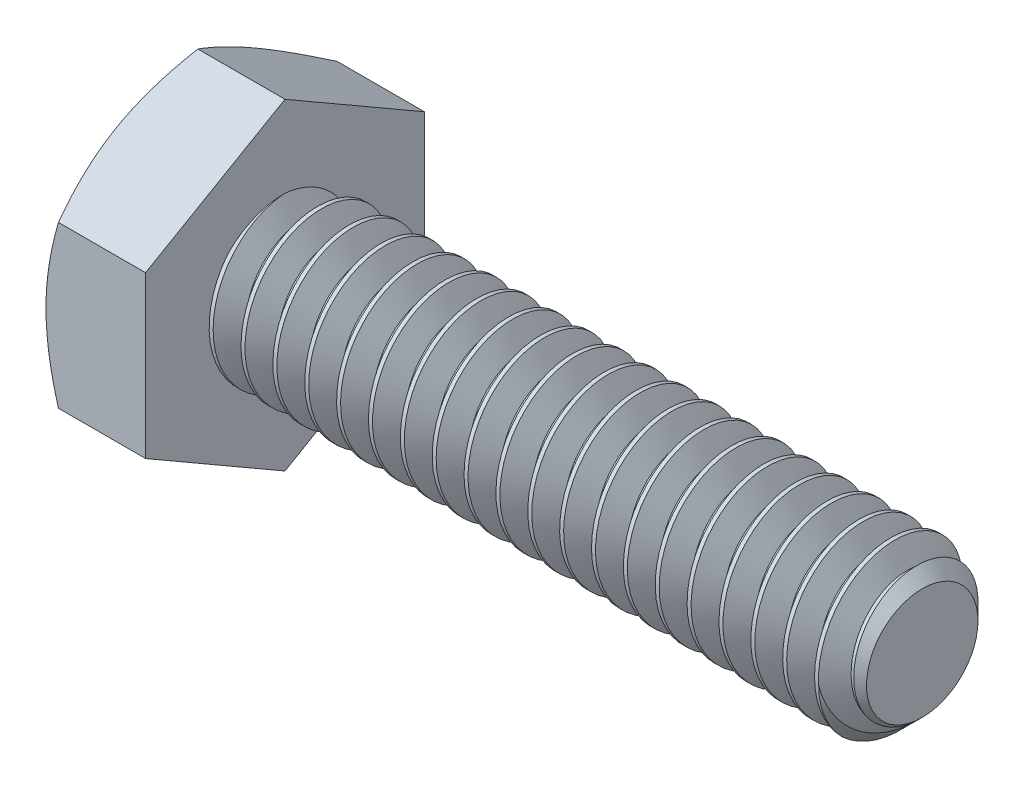
SolidWorks part; units mm, degrees
material "AISI 304"
ref_plane "Front Plane" through (0, 0, 0) normal (0, 0, 1) x (1, 0, 0)
ref_plane "Top Plane" through (0, 0, 0) normal (0, 1, 0) x (1, 0, 0)
ref_plane "Right Plane" through (0, 0, 0) normal (1, 0, 0) x (0, 0, -1)
sketch "Sketch1" plane through (0, 0, 0) normal (0, 0, 1) x (1, 0, 0)
  line L0 (-14.6844, 0) -> (14.6844, 0) construction
  line L1 (14.6844, 3.175) -> (14.6844, -3.175) construction
  line L2 (-10.7156, 5.5562) -> (-10.7156, -5.5562) construction
  line L3 (-14.6844, 5.5562) -> (-14.6844, -5.5562) construction
  point P9 (-10.7156, 0)
  point P10 (10.2394, -3.175)
  dimension "D1" = 4.445
  dimension "Screw Dia" = 6.35
  dimension "Hex" = 11.1125
  dimension "Head Ht" = 3.9688
  dimension "Screw Lenght" = 25.4
ref_plane "Plane2" through (14.6844, 0, 0) normal (1, 0, 0) x (0, 0, -1)
sketch "Sketch5" plane through (14.6844, 0, 0) normal (1, 0, 0) x (0, 0, -1)
  circle A0 centre (0, 0) radius 3.175
extrude "Boss-Extrude3" add sketch "Sketch5" against normal up to vertex (25.4 mm away) up to point (-10.7156, 0, 0)
sketch "Sketch9" plane through (14.6844, 0, 0) normal (1, 0, 0) x (0, 0, -1)
  circle A1 centre (0, 0) radius 3.175
  circle A2 centre (0, 0) radius 3.175
  dimension "D1" = 0
curve "Helix/Spiral1" pitch 1.27 height 26.67 turns 21 parameters "Pitch"=1.27
chamfer "Chamfer1" distance 0.9525 angle 45 1 edges at (14.6844, 0, -3.175)
sketch "Sketch10" plane through (0, 0, 0) normal (0, 0, 1) x (1, 0, 0)
  line L0 (14.6844, 3.175) -> (15.1606, 2.3501)
  line L1 (15.1606, 2.3501) -> (15.3194, 2.3501)
  line L2 (15.3194, 2.3501) -> (15.7956, 3.175)
  line L3 (14.6844, 3.175) -> (15.7956, 3.175)
  line L4 (15.24, 3.175) -> (15.24, 2.3501) construction
  line L5 (14.9225, 2.7626) -> (15.5575, 2.7626) construction
  dimension "D1" = 60
  dimension "D2" = 0.1588
  dimension "D3" = 0.635
sweep "Cut-Sweep1" cut profiles "Sketch10" path "Helix/Spiral1"
sketch "Sketch6" plane through (-10.7156, 0, 0) normal (-1, 0, 0) x (0, 0, 1)
  line L0 (0, 5.5562) -> (0, -5.5562) construction
  line L1 (5.5562, 3.2079) -> (0, 6.4158)
  line L2 (0, 6.4158) -> (-5.5562, 3.2079)
  line L3 (-5.5562, 3.2079) -> (-5.5562, -3.2079)
  line L4 (-5.5562, -3.2079) -> (0, -6.4158)
  line L5 (0, -6.4158) -> (5.5562, -3.2079)
  line L6 (5.5562, -3.2079) -> (5.5562, 3.2079)
  circle A0 centre (0, 0) radius 5.5562 construction
extrude "Boss-Extrude4" add sketch "Sketch6" along normal up to vertex (3.9688 mm away) up to point (-14.6844, -5.5562, 0)
sketch "Sketch7" plane through (-14.6844, 0, 0) normal (-1, 0, 0) x (0, 0, 1)
  circle A0 centre (0, 0) radius 5.5562 construction
  circle A1 centre (0, 0) radius 5.5562
sketch "Sketch8" plane through (-14.6844, 0, 0) normal (-1, 0, 0) x (0, 0, 1)
  circle A0 centre (0, 0) radius 5.5562 construction
  circle A1 centre (0, 0) radius 5.5562
extrude "Cut-Extrude3" cut sketch "Sketch8" against normal through all draft 60 flip side to cut
equation "\"D2@Sketch10\" = \"Pitch@Helix/Spiral1\"*.125"
equation "\"D3@Sketch10\" = \"Pitch@Helix/Spiral1\"*.5"
equation "\"D3@Helix/Spiral1\" = \"Screw Lenght@Sketch1\"+\"Pitch@Helix/Spiral1\""
equation "\"D1@Chamfer1\" = \"Pitch@Helix/Spiral1\"*.75"
equation "\"D1@Sketch1\" = \"Pitch@Helix/Spiral1\"*3.5"
